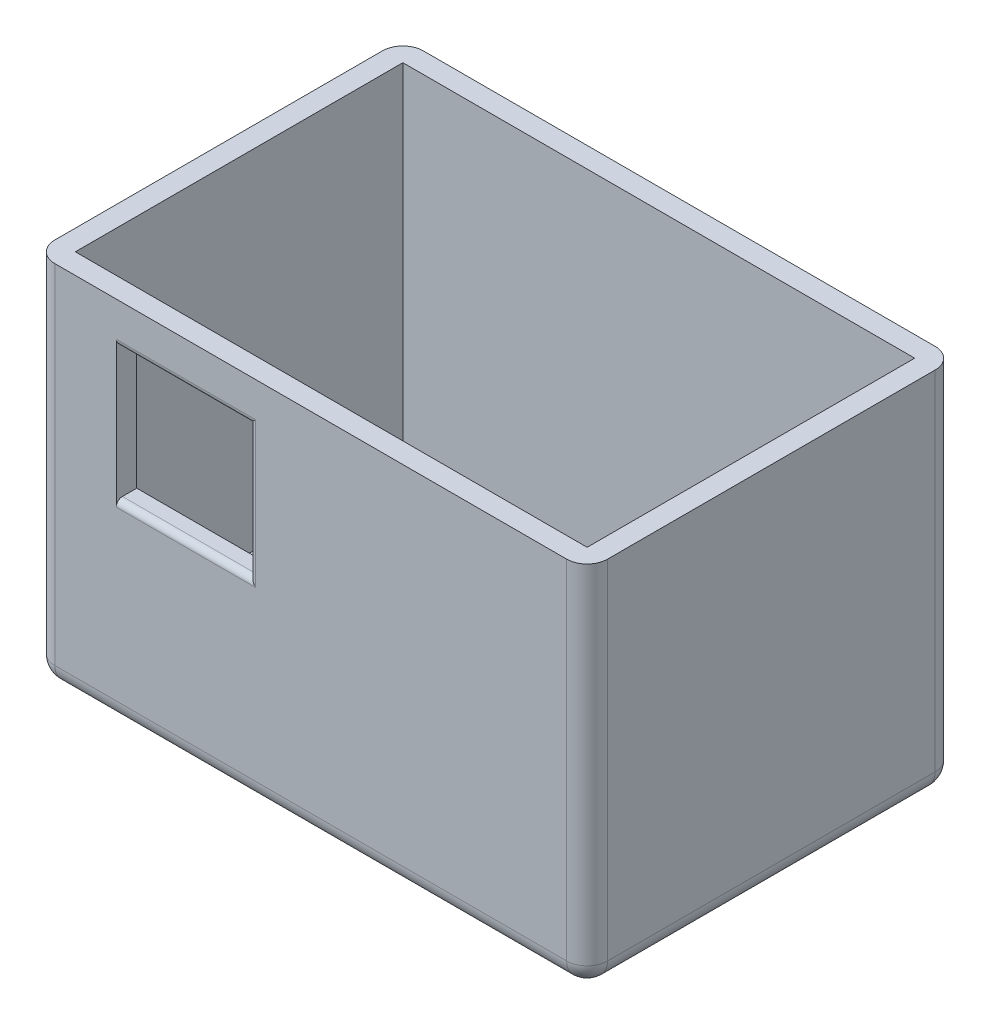
SolidWorks part; units mm, degrees
ref_plane "前视基准面" through (0, 0, 0) normal (0, 0, 1) x (1, 0, 0)
ref_plane "上视基准面" through (0, 0, 0) normal (0, 1, 0) x (1, 0, 0)
ref_plane "右视基准面" through (0, 0, 0) normal (1, 0, 0) x (0, 0, -1)
sketch "Sketch1" plane through (0, 0, 0) normal (0, 1, 0) x (1, 0, 0)
  line L1 (-135, -90) -> (135, -90)
  line L2 (-135, -90) -> (-135, 90)
  line L3 (-135, 90) -> (135, 90)
  line L4 (135, -90) -> (135, 90)
  line L5 (-135, -90) -> (135, 90) construction
  line L6 (-135, 90) -> (135, -90) construction
  point P0 (0, 0)
  dimension "D1" = 270
  dimension "D2" = 180
extrude "Extrude1" add sketch "Sketch1" along normal blind 180
fillet "Fillet1" radius 10 8 edges at (-135, 0, 0) (0, 0, 90) (135, 0, 0) (0, 0, -90) (135, 90, 90) (135, 90, -90) (-135, 90, -90) (-135, 90, 90)
shell "Shell1" thickness 10 removed face at (0, 180, 0)
sketch "Sketch2" plane through (0, 0, 90) normal (0, 0, 1) x (1, 0, 0)
  line L1 (-95, 160) -> (-30, 160)
  line L2 (-95, 160) -> (-95, 95)
  line L3 (-95, 95) -> (-30, 95)
  line L4 (-30, 160) -> (-30, 95)
  dimension "D1" = 65
  dimension "D2" = 65
  dimension "D3" = 20
  dimension "D4" = 30
extrude "Extrude2" cut sketch "Sketch2" against normal blind 20
fillet "Fillet2" radius 3 3 edges at (-62.5, 95, 90) (-30, 127.5, 90) (-62.5, 160, 90)
